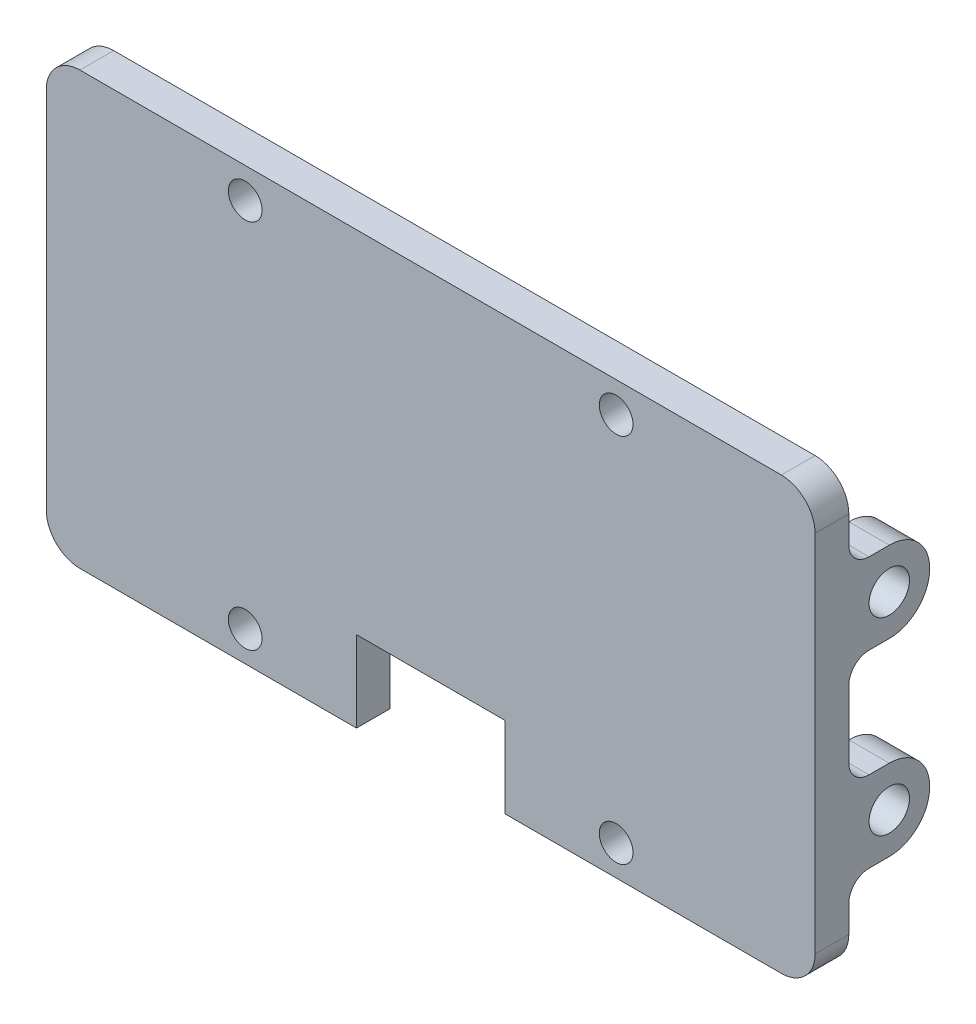
SolidWorks part; units mm, degrees
ref_plane "前视基准面" through (0, 0, 0) normal (0, 0, 1) x (1, 0, 0)
ref_plane "上视基准面" through (0, 0, 0) normal (0, 1, 0) x (1, 0, 0)
ref_plane "右视基准面" through (0, 0, 0) normal (1, 0, 0) x (0, 0, -1)
sketch "草图1" plane through (0, 0, 0) normal (0, 0, 1) x (1, 0, 0)
  line L1 (-16, -16) -> (16, -16)
  line L3 (-16, 16) -> (16, 16)
  line L13 (0, -10) -> (5.5, -10)
  line L14 (5.5, -10) -> (5.5, -16)
  line L15 (5.5, -16) -> (-5.5, -16)
  line L16 (-5.5, -16) -> (-5.5, -10)
  line L17 (-5.5, -10) -> (0, -10)
  line L18 (-28.5, -16) -> (28.5, -16)
  line L19 (-28.5, -16) -> (-28.5, 16)
  line L20 (-28.5, 16) -> (28.5, 16)
  line L21 (28.5, -16) -> (28.5, 16)
  circle A0 centre (-13.75, 13.75) radius 1.25
  circle A1 centre (13.75, 13.75) radius 1.25
  circle A2 centre (-13.75, -13.75) radius 1.25
  circle A3 centre (13.75, -13.75) radius 1.25
  point P0 (0, 0)
  point P6 (0, 0)
  point P15 (0, 0)
extrude "凸台-拉伸1" add sketch "草图1" along normal blind 2.5 contours L16 L17 L13 L14 L1 L3 A3 A2 A1 A0 region at (0, 0.4936, 0)
sketch "草图3" plane through (-28.5, 0, 0) normal (-1, 0, 0) x (0, 0, 1)
  line L0 (-3, 4) -> (0, 4)
  line L2 (0, -16) -> (0, 16) construction
  line L3 (0, 4) -> (0, 10)
  line L4 (0, 10) -> (-3, 10)
  line L5 (-3, -4) -> (0, -4)
  line L6 (0, -4) -> (0, -10)
  line L7 (0, -10) -> (-3, -10)
  circle A0 centre (-3, 7) radius 1.5
  circle A1 centre (-3, -7) radius 1.5
  arc A2 (-3, 10) -> (-3, 4) centre (-3, 7) ccw
  arc A3 (-3, -4) -> (-3, -10) centre (-3, -7) ccw
extrude "凸台-拉伸2" add sketch "草图3" against normal blind 3
sketch "草图4" plane through (28.5, 0, 0) normal (1, 0, 0) x (0, 0, -1)
  line L0 (3, -4) -> (0, -4) construction
  line L1 (0, -4) -> (0, -10) construction
  line L2 (0, -10) -> (3, -10) construction
  line L3 (3, 10) -> (0, 10) construction
  line L4 (0, 10) -> (0, 4) construction
  line L5 (0, 4) -> (3, 4) construction
  line L6 (3, -4) -> (0, -4)
  line L7 (0, -4) -> (0, -10)
  line L8 (0, -10) -> (3, -10)
  line L9 (3, 10) -> (0, 10)
  line L10 (0, 10) -> (0, 4)
  line L11 (0, 4) -> (3, 4)
  arc A0 (3, -10) -> (3, -4) centre (3, -7) ccw construction
  arc A1 (3, 4) -> (3, 10) centre (3, 7) ccw construction
  arc A2 (3, -10) -> (3, -4) centre (3, -7) ccw
  arc A3 (3, 4) -> (3, 10) centre (3, 7) ccw
  circle A4 centre (3, -7) radius 1.5 construction
  circle A5 centre (3, 7) radius 1.5 construction
  circle A6 centre (3, -7) radius 1.5
  circle A7 centre (3, 7) radius 1.5
extrude "凸台-拉伸3" add sketch "草图4" against normal blind 3
fillet "圆角1" radius 1.5 12 edges at (27, -4, 0) (27, 10, 0) (27, -10, 0) (27, 4, 0) (-25.5, 7, 0) (-25.5, -7, 0) (-27, -10, 0) (-27, 10, 0) (-27, -4, 0) (-27, 4, 0) (25.5, -7, 0) (25.5, 7, 0)
fillet "圆角2" radius 2.5 4 edges at (-28.5, -16, 1.25) (28.5, -16, 1.25) (-28.5, 16, 1.25) (28.5, 16, 1.25)
